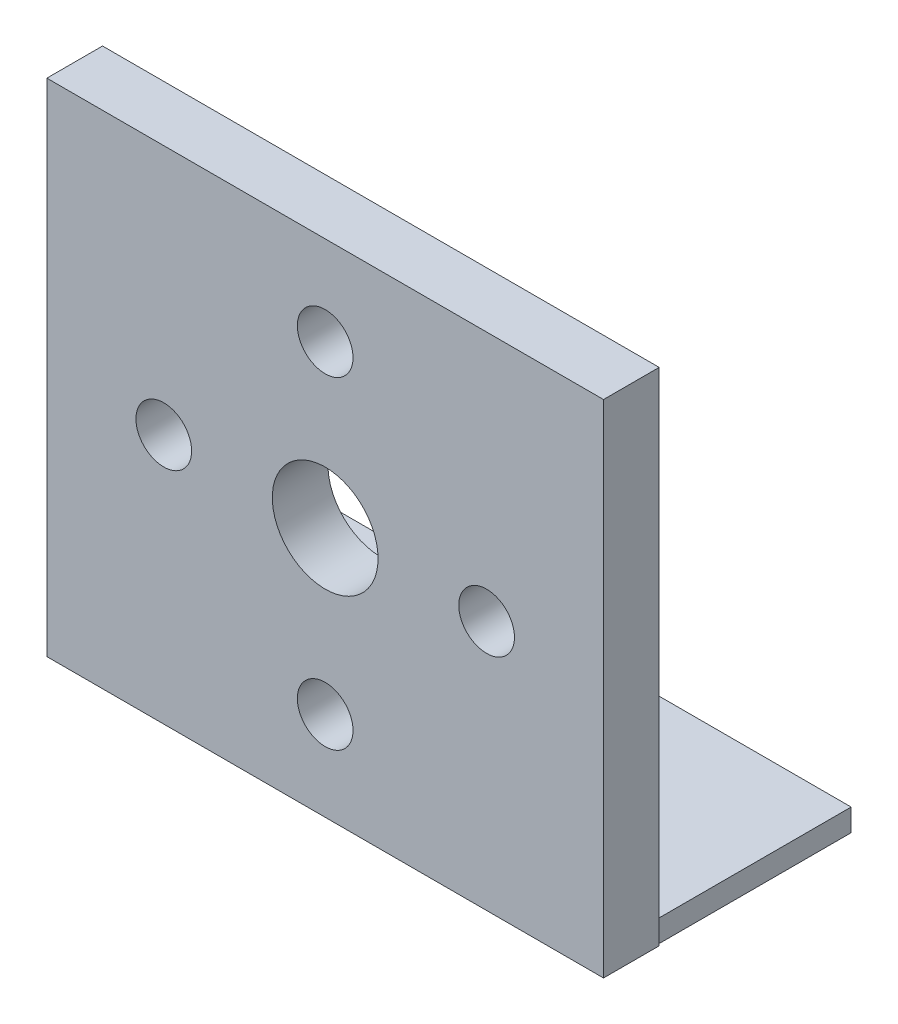
SolidWorks part; units mm, degrees
ref_plane "Front Plane" through (0, 0, 0) normal (0, 0, 1) x (1, 0, 0)
ref_plane "Top Plane" through (0, 0, 0) normal (0, 1, 0) x (1, 0, 0)
ref_plane "Right Plane" through (0, 0, 0) normal (1, 0, 0) x (0, 0, -1)
sketch "Sketch1" plane through (0, 0, 0) normal (0, 0, 1) x (1, 0, 0)
  line L1 (25, -22.5) -> (-25, -22.5)
  line L2 (25, -22.5) -> (25, 22.5)
  line L3 (25, 22.5) -> (-25, 22.5)
  line L4 (-25, -22.5) -> (-25, 22.5)
  line L5 (25, -22.5) -> (-25, 22.5) construction
  line L6 (25, 22.5) -> (-25, -22.5) construction
  line L7 (25.0909, -22.4163) -> (-24.9091, -22.4163)
  line L8 (25.0909, -22.4163) -> (25.0909, -20.4163)
  line L10 (-24.9091, -22.4163) -> (-24.9091, -20.4163)
  circle A0 centre (0, 0) radius 4.75
  circle A1 centre (0, -14.5) radius 2.5
  circle A4 centre (-14.5, 0) radius 2.5
  circle A5 centre (0, 14.5) radius 2.5
  circle A6 centre (14.5, 0) radius 2.5
  point P0 (0, 0)
  point P23 (0, 0)
  dimension "D5" = 8
  dimension "D1" = 45
  dimension "D2" = 50
  dimension "D3" = 22.5
  dimension "D4" = 25
  dimension "D6" = 25
  dimension "D7" = 4
extrude "Boss-Extrude3" add sketch "Sketch1" along normal blind 2.5 and the other way blind 2.5 contours L4 L1 L2 L3 A6 A5 A4 A1 A0 region at (0, -21.8273, 0)
sketch "Sketch2" plane through (0, 0, 0) normal (0, 0, 1) x (1, 0, 0)
  line L0 (8.75, -22.0588) -> (-8.5008, -22.3686) construction
  line L1 (24.743, -22.5786) -> (-24.8148, -22.5786)
  line L2 (24.743, -22.5786) -> (24.743, -20.5786)
  line L3 (24.743, -20.5786) -> (-24.8148, -20.5786)
  line L4 (-24.8148, -22.5786) -> (-24.8148, -20.5786)
  circle A2 centre (8.75, -22.0588) radius 0.5 construction
  dimension "D1" = 2
extrude "Boss-Extrude4" add sketch "Sketch2" against normal blind 20
sketch "Sketch4" plane through (0, 0, 0) normal (0, 0, 1) x (1, 0, 0)
  line L0 (25, -22.5) -> (25, 22.5) construction
  line L2 (-25, -22.5) -> (-25, 22.5) construction
  circle A0 centre (-8.75, -21.873) radius 0.5
  circle A1 centre (8.75, -22.0588) radius 0.5
  point P4 (0, 0)
  point P5 (-18.2181, -21.5597)
  point P6 (8.7238, -21.8102)
  point P7 (0, 0)
  point P8 (-18.8276, -21.8239)
  point P9 (9.4297, -21.7536)
  point P14 (-6.25, -21.873)
  point P15 (11.25, -22.0588)
  point P16 (0, 0)
  point P17 (0, 0)
  point P18 (0, 0)
  dimension "D1" = 17.5
  dimension "D2" = 16.25
  dimension "D3" = 16.25
